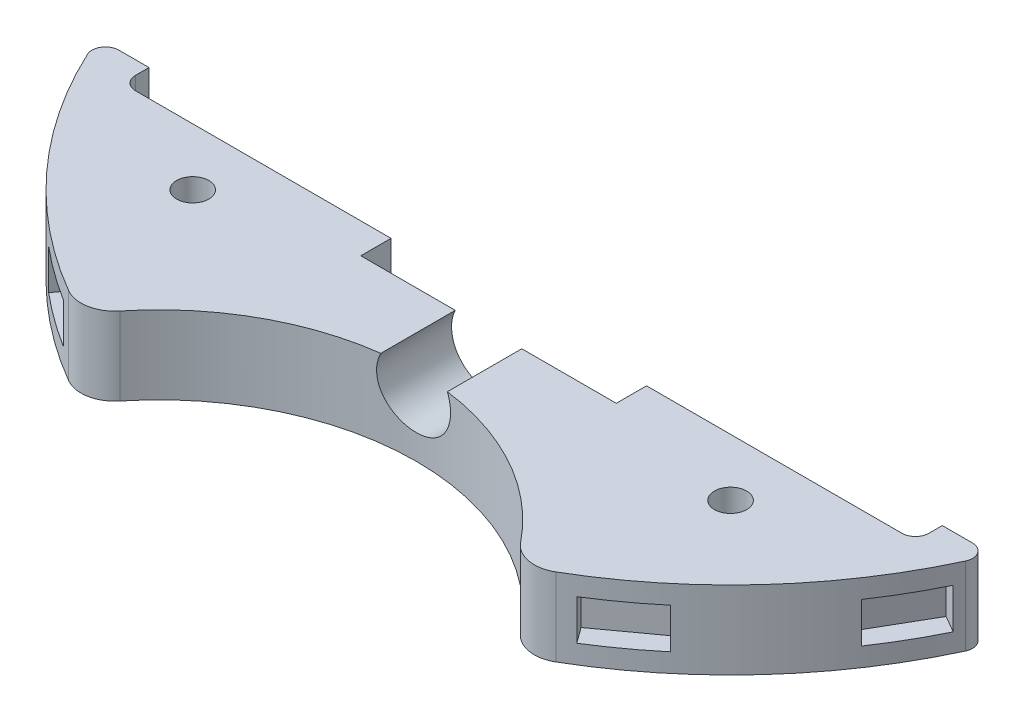
SolidWorks part; units mm, degrees
material "ABS"
ref_plane "Front Plane" through (0, 0, 0) normal (0, 0, 1) x (1, 0, 0)
ref_plane "Top Plane" through (0, 0, 0) normal (0, 1, 0) x (1, 0, 0)
ref_plane "Right Plane" through (0, 0, 0) normal (1, 0, 0) x (0, 0, -1)
sketch "Sketch1" plane through (0, 0, 0) normal (0, 1, 0) x (1, 0, 0)
  line L0 (0, -85) -> (-32.2211, -64.3879) construction
  line L1 (0, -85) -> (0, 0) construction
  arc A0 (36.2245, -62.2237) -> (-36.2245, -62.2237) centre (0, 0) ccw
  arc A1 (29.8119, -61.0352) -> (-29.8119, -61.0352) centre (0, -85) ccw
  arc A2 (36.2245, -62.2237) -> (29.8119, -61.0352) centre (33.7089, -57.9026) cw
  arc A3 (-29.8119, -61.0352) -> (-36.2245, -62.2237) centre (-33.7089, -57.9026) cw
  dimension "D1" = 144
  dimension "D2" = 76.5
  dimension "D4" = 5
  dimension "D3" = 85
extrude "Boss-Extrude1" add sketch "Sketch1" along normal mid plane 11.6
sketch "solenoid placement" plane through (0, 5.8, 0) normal (0, 1, 0) x (1, 0, 0)
  line L0 (0, 0) -> (0, -36) construction
  line L5 (-19, -36) -> (19, -36)
  line L7 (19, -36) -> (19, 28)
  line L9 (19, 28) -> (-19, 28)
  line L11 (-19, 28) -> (-19, -36)
  circle A1 centre (0, 0) radius 72 construction
  arc A2 (36.2245, -62.2237) -> (-36.2245, -62.2237) centre (0, 0) ccw construction
  point P7 (0, 28)
  dimension "D1" = 38
  dimension "D2" = 64
  dimension "D3" = 36
extrude "Cut-Extrude1" cut sketch "solenoid placement" against normal through all
sketch "Sketch6" plane through (0, 5.8, 0) normal (0, 1, 0) x (1, 0, 0)
  line L0 (0, 0) -> (0, -46.75) construction
  arc A0 (29.8119, -61.0352) -> (-29.8119, -61.0352) centre (0, -85) ccw construction
  circle A1 centre (40, -40) radius 2.4
  circle A4 centre (-40, -40) radius 2.4
  dimension "D1" = 4.8
  dimension "D2" = 40
  dimension "D3" = 40
extrude "Cut-Extrude6" cut sketch "Sketch6" against normal through all
sketch "Sketch3" plane through (0, 5.8, 0) normal (0, 1, 0) x (1, 0, 0)
  line L0 (-72, -27.5) -> (-59, -27.5)
  line L1 (-59, -31.5) -> (59, -31.5)
  line L2 (-72, -27.5) -> (-72, 31.5)
  line L3 (-59, -27.5) -> (-59, -31.5)
  line L4 (72, -27.5) -> (72, 31.5)
  line L5 (-72, 31.5) -> (72, 31.5) construction
  line L6 (0, 31.5) -> (0, -31.5) construction
  line L7 (59, -27.5) -> (59, -31.5)
  line L8 (-72, 31.5) -> (-72, 72)
  line L9 (72, -27.5) -> (59, -27.5)
  line L10 (-72, 72) -> (72, 72)
  line L11 (72, 31.5) -> (72, 72)
  arc A0 (36.2245, -62.2237) -> (-36.2245, -62.2237) centre (0, 0) ccw construction
  arc A1 (36.2245, -62.2237) -> (-36.2245, -62.2237) centre (0, 0) ccw construction
  point P0 (0, 0)
  dimension "D2" = 4
  dimension "D1" = 63
  dimension "D3" = 13
extrude "Cut-Extrude3" cut sketch "Sketch3" against normal through all
fillet "Fillet1" radius 2 4 edges at (66.5413, 0, 27.5) (59, 0, 31.5) (-66.5413, 0, 27.5) (-59, 0, 31.5)
sketch "Sketch8" plane through (0, 0, 0) normal (0, 1, 0) x (1, 0, 0)
  line L0 (0, 0) -> (62.3538, -36) construction
  line L1 (0, 0) -> (42.3205, -58.2492) construction
  line L2 (0, 0) -> (14.9696, -70.4266) construction
  line L3 (0, 0) -> (-14.9696, -70.4266) construction
  line L4 (-42.3205, -58.2492) -> (0, 0) construction
  line L5 (0, 0) -> (-62.3538, -36) construction
  line L6 (0, 0) -> (0, -72) construction
  arc A0 (-62.3538, -36) -> (-42.3205, -58.2492) centre (0, 0) ccw construction
  arc A1 (62.3538, -36) -> (42.3205, -58.2492) centre (0, 0) cw construction
  arc A2 (14.9696, -70.4266) -> (42.3205, -58.2492) centre (0, 0) ccw construction
  arc A3 (14.9696, -70.4266) -> (-14.9696, -70.4266) centre (0, 0) cw construction
  arc A4 (-14.9696, -70.4266) -> (-42.3205, -58.2492) centre (0, 0) cw construction
  arc A5 (36.2245, -62.2237) -> (65.294, -30.3429) centre (0, 0) ccw construction
  dimension "D1" = 120
sketch "Sketch9" plane through (0, 0, 0) normal (0, 1, 0) x (1, 0, 0)
  line L0 (0, 0) -> (-59.7033, -40.2432) construction
  line L1 (0, 0) -> (-64.7033, -31.583) construction
  line L2 (-64.7033, -31.583) -> (-59.7033, -40.2432) construction
  line L3 (-64.7033, -31.583) -> (-62.1918, -30.133)
  line L4 (-62.1918, -30.133) -> (-57.1918, -38.7932)
  line L5 (-57.1918, -38.7932) -> (-59.7033, -40.2432)
  line L6 (-46.2635, -55.1697) -> (-44.5589, -52.8235)
  line L7 (-44.5589, -52.8235) -> (-36.4687, -58.7014)
  line L8 (-36.4687, -58.7014) -> (-38.1733, -61.0475)
  line L9 (0, 0) -> (-38.1733, -61.0475) construction
  line L10 (0, 0) -> (-46.2635, -55.1697) construction
  line L11 (-46.2635, -55.1697) -> (-38.1733, -61.0475) construction
  line L12 (-19.8242, -69.217) -> (-19.2213, -66.3804) [skipped]
  line L13 (-19.2213, -66.3804) -> (-9.4398, -68.4595) [skipped]
  line L14 (-9.4398, -68.4595) -> (-10.0428, -71.2962) [skipped]
  line L15 (0, 0) -> (-10.0428, -71.2962) construction
  line L16 (0, 0) -> (-19.8242, -69.217) construction
  line L17 (-19.8242, -69.217) -> (-10.0428, -71.2962) construction
  line L18 (10.0428, -71.2962) -> (9.4398, -68.4595) [skipped]
  line L19 (9.4398, -68.4595) -> (19.2213, -66.3804) [skipped]
  line L20 (19.2213, -66.3804) -> (19.8242, -69.217) [skipped]
  line L21 (0, 0) -> (19.8242, -69.217) construction
  line L22 (0, 0) -> (10.0428, -71.2962) construction
  line L23 (10.0428, -71.2962) -> (19.8242, -69.217) construction
  line L24 (38.1733, -61.0475) -> (36.4687, -58.7014)
  line L25 (36.4687, -58.7014) -> (44.5589, -52.8235)
  line L26 (44.5589, -52.8235) -> (46.2635, -55.1697)
  line L27 (0, 0) -> (46.2635, -55.1697) construction
  line L28 (0, 0) -> (38.1733, -61.0475) construction
  line L29 (38.1733, -61.0475) -> (46.2635, -55.1697) construction
  line L30 (59.7033, -40.2432) -> (57.1918, -38.7932)
  line L31 (57.1918, -38.7932) -> (62.1918, -30.133)
  line L32 (62.1918, -30.133) -> (64.7033, -31.583)
  line L33 (0, 0) -> (64.7033, -31.583) construction
  line L34 (0, 0) -> (59.7033, -40.2432) construction
  line L35 (59.7033, -40.2432) -> (64.7033, -31.583) construction
  arc A0 (-59.7033, -40.2432) -> (-64.7033, -31.583) centre (0, 0) cw
  arc A1 (-62.3538, -36) -> (-42.3205, -58.2492) centre (0, 0) ccw construction
  arc A2 (-38.1733, -61.0475) -> (-46.2635, -55.1697) centre (0, 0) cw
  arc A3 (-10.0428, -71.2962) -> (-19.8242, -69.217) centre (0, 0) cw [skipped]
  arc A4 (19.8242, -69.217) -> (10.0428, -71.2962) centre (0, 0) cw [skipped]
  arc A5 (46.2635, -55.1697) -> (38.1733, -61.0475) centre (0, 0) cw
  arc A6 (64.7033, -31.583) -> (59.7033, -40.2432) centre (0, 0) cw
  point P8 (-62.3538, -36)
  point P12 (62.3538, -36)
  point P34 (0, 0)
  dimension "D1" = 10
  dimension "D2" = 2.9
  dimension "D3" = 6
extrude "Cut-Extrude7" cut sketch "Sketch9" against normal mid plane 6
sketch "Sketch11" plane through (0, 0, 36) normal (0, 0, -1) x (-1, 0, 0)
  line L0 (0, -5.8) -> (0, 3.4) construction
  line L1 (19, -5.8) -> (-19, -5.8) construction
  circle A0 centre (0, 3.4) radius 5.5
  dimension "D2" = 11
  dimension "D1" = 9.2
extrude "Cut-Extrude8" cut sketch "Sketch11" against normal through all
equation "\"smallPulleyTeeth\"= 15"
equation "\"largePulleyTeeth\"= 30"
equation "\"eighthThick\"= 2.9mm"
equation "\"sixteenthThick\" = 1.7mm"
equation "\"quarterThick\"=6.0mm"
equation "\"OD\" = 146mm"
equation "\"puckAngle\" = 60.5deg"
equation "\"puckDiam\" = 76.5mm"
equation "\"D2@Sketch1\"=\"puckDiam\""
equation "\"D1@Boss-Extrude1\"=\"eighthThick\"*4"
equation "\"axlePress\" = 5.9mm"
equation "\"press\" = 0.2mm"
equation "\"wheelClear\" = 0.3mm"
equation "\"10-32clear\" = 4.8mm"
equation "\"6-32clear\" = 3.3mm"
equation "\"8-32clear\" = 4.0mm"
equation "\"wheelHeight\" = 22mm"
equation "\"wheelWell\" = 65mm"
equation "\"puckDist\" = 85mm"
equation "\"scoopFillet\" = 5mm"
equation "\"4-40clear\" = 3.0mm"
equation "\"D3@Sketch1\"=\"puckDist\""
equation "\"D4@Sketch1\"=\"scoopFillet\""
equation "\"D1@Sketch6\"=\"10-32clear\""
equation "\"D2@Sketch9\"=\"eighthThick\""
